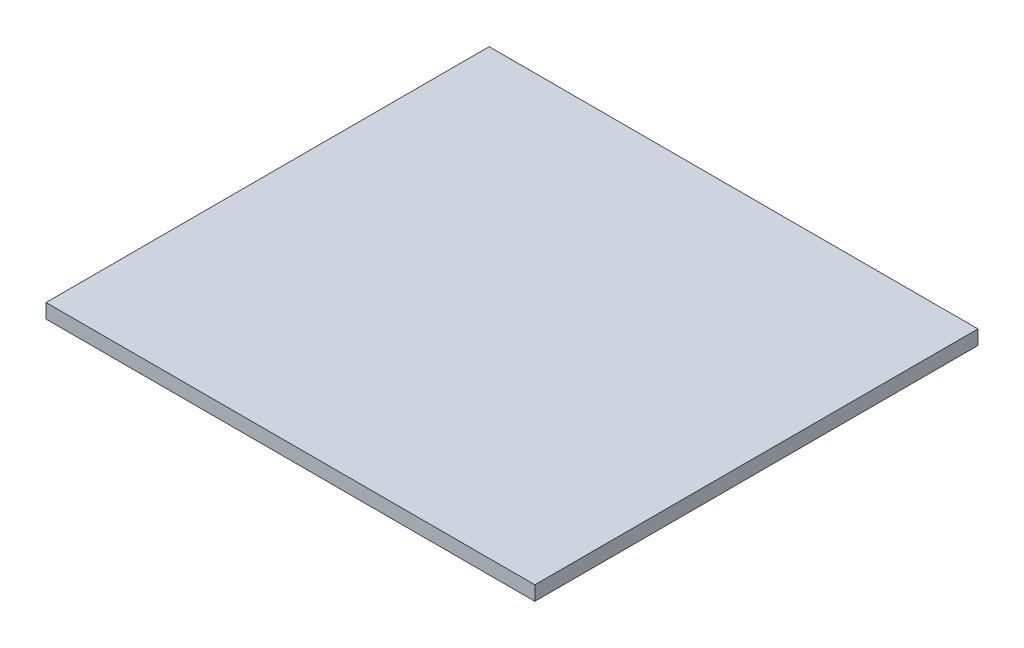
SolidWorks part; units mm, degrees
ref_plane "Front Plane" through (0, 0, 0) normal (0, 0, 1) x (1, 0, 0)
ref_plane "Top Plane" through (0, 0, 0) normal (0, 1, 0) x (1, 0, 0)
ref_plane "Right Plane" through (0, 0, 0) normal (1, 0, 0) x (0, 0, -1)
sketch "Sketch1" plane through (0, 0, 0) normal (0, 1, 0) x (1, 0, 0)
  line L1 (-44.2815, 20.698) -> (64.7185, 20.698)
  line L2 (-44.2815, 20.698) -> (-44.2815, -78.102)
  line L3 (-44.2815, -78.102) -> (64.7185, -78.102)
  line L4 (64.7185, 20.698) -> (64.7185, -78.102)
  dimension "D1" = 109
  dimension "D2" = 98.8
extrude "Boss-Extrude1" add sketch "Sketch1" along normal blind 3.2
equation "\"Fit\"= 1"
equation "\"cover width\"= 98.8"
equation "\"top 2-3-4-5 length\"= 109"
equation "\"thinner acrylic\"= 3.2"
equation "\"D1@Sketch1\"=\"top 2-3-4-5 length\""
equation "\"D2@Sketch1\"=\"cover width\""
equation "\"D1@Boss-Extrude1\"=\"thinner acrylic\""
